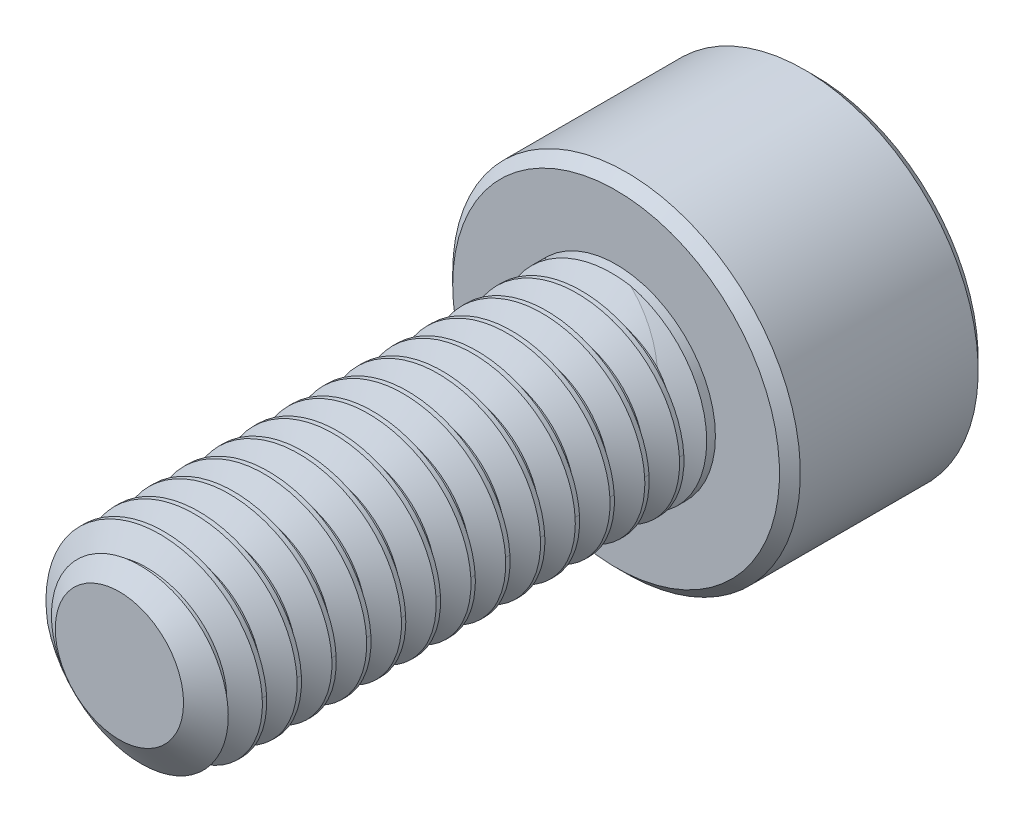
SolidWorks part; units mm, degrees
material "Alloy Steel"
ref_plane "Front Plane" through (0, 0, 0) normal (0, 0, 1) x (1, 0, 0)
ref_plane "Top Plane" through (0, 0, 0) normal (0, 1, 0) x (1, 0, 0)
ref_plane "Right Plane" through (0, 0, 0) normal (1, 0, 0) x (0, 0, -1)
sketch "Sketch1" plane through (0, 0, 0) normal (0, 0, 1) x (1, 0, 0)
  circle A0 centre (0, 0) radius 2
  dimension "OD" = 4
extrude "Extrude1" add sketch "Sketch1" against normal blind 10
sketch "Sketch2" plane through (0, 0, 0) normal (0, 0, 1) x (1, 0, 0)
  circle A0 centre (0, 0) radius 2 construction
  circle A1 centre (0, 0) radius 2
curve "Helix/Spiral1" pitch 0.7 height 10.7 radius 2 centre (0, 0, 0) axis (0, 0, -1) start towards (0, 1, 0) parameters "pitch"=0.7
sketch "Sketch3" plane through (0, 0, 0) normal (1, 0, 0) x (0, 0, -1)
  line L0 (-0.6125, 2) -> (-0.35, 1.5453)
  line L1 (-0.35, 1.5453) -> (-0.2625, 1.5453)
  line L2 (-0.2625, 1.5453) -> (0, 2)
  line L3 (-0.6125, 2) -> (0, 2)
  line L4 (-0.3063, 2) -> (-0.3063, 1.5453) construction
  line L5 (-0.4813, 1.7727) -> (-0.1313, 1.7727) construction
  line L6 (0, 2) -> (0, -2) construction
  line L7 (0, -2) -> (10, -2) construction
  point P11 (3.15, -2)
  dimension "D1" = 0.0875
  dimension "D2" = 0.35
  dimension "D3" = 60
  dimension "D4" = 3.15
sweep "Cut-Sweep1" cut profiles "Sketch3" path "Helix/Spiral1"
sketch "Sketch4" plane through (0, 0, 0) normal (1, 0, 0) x (0, 0, -1)
  line L0 (0.4962, 2) -> (0, 1.2913)
  line L1 (0, 1.2913) -> (0, 2)
  line L2 (0.4962, 2) -> (0, 2)
  line L3 (-0.6125, 2) -> (0, 2) construction
  line L4 (0, 0) -> (7.0209, 0) construction
  dimension "D1" = 55
  dimension "D2" = 0.254
revolve "Cut-Revolve1" cut sketch "Sketch4" angle 360 about L4
sketch "Sketch5" plane through (0, 0, 0) normal (1, 0, 0) x (0, 0, -1)
  line L0 (10, 0.3311) -> (10, 1.814) construction
  line L1 (10, 2) -> (0.1203, 2)
  line L2 (10, 2) -> (10, 0)
  line L3 (10, 0) -> (0.0001, 0)
  line L4 (0.0001, 1.6698) -> (0.0001, 0)
  line L5 (0.1203, 2) -> (0.0001, 1.6698)
  line L6 (0, 0) -> (9.9695, 0) construction
  point P3 (0.0001, 2)
  point P10 (0.0001, 2)
  dimension "D1" = 0.3302
  dimension "Thread min" = 0.0001
  dimension "D3" = 20
revolve "partially thread" [suppressed] add sketch "Sketch5" angle 360 about L6
sketch "Sketch6" plane through (0, 0, -10) normal (0, 0, -1) x (-1, 0, 0)
  circle A0 centre (0, 0) radius 3.5
  dimension "head dia" = 7
extrude "Extrude2" add sketch "Sketch6" along normal blind 4
sketch "Sketch7" plane through (0, 0, -14) normal (0, 0, -1) x (-1, 0, 0)
  line L1 (0, 1.7321) -> (-1.5, 0.866)
  line L2 (-1.5, 0.866) -> (-1.5, -0.866)
  line L3 (-1.5, -0.866) -> (0, -1.7321)
  line L4 (0, -1.7321) -> (1.5, -0.866)
  line L5 (1.5, -0.866) -> (1.5, 0.866)
  line L6 (1.5, 0.866) -> (0, 1.7321)
  circle A0 centre (0, 0) radius 1.5 construction
  dimension "hex dia" = 3
extrude "Cut-Extrude1" cut sketch "Sketch7" against normal blind 2.25
sketch "Sketch8" plane through (0, 0, -14) normal (0, 0, -1) x (-1, 0, 0)
  circle A0 centre (0, 0) radius 1.7321
extrude "Cut-Extrude2" cut sketch "Sketch8" against normal through all draft 45
chamfer "Chamfer1" distance 0.21 angle 45 2 edges at (-3.5, 0, -14) (-3.5, 0, -10)
sketch "Sketch9" plane through (0, 0, 0) normal (1, 0, 0) x (0, 0, -1)
  line L0 (0, 2) -> (0, -2) construction
  line L1 (3.85, 2) -> (3.85, -2) construction
  dimension "D1" = 3.85
sketch "Sketch10" plane through (0, 0, 0) normal (1, 0, 0) x (0, 0, -1)
  line L0 (10, 2) -> (10, 0)
  line L1 (10, 2) -> (9.825, 2)
  line L2 (9.825, 2) -> (8.9966, 0)
  line L3 (10, 0) -> (8.9966, 0)
  line L4 (10, 3.29) -> (10, -3.29) construction
  dimension "D1" = 22.5
  dimension "D2" = 0.175
revolve "Revolve1" add sketch "Sketch10" angle 360 about L3
equation "\"D3@Helix/Spiral1\" = \"screw length@Extrude1\"+\"pitch@Helix/Spiral1\""
equation "\"D1@Sketch3\" = \"pitch@Helix/Spiral1\"*.125"
equation "\"D2@Sketch3\" = \"pitch@Helix/Spiral1\"*.5"
equation "\"D1@Cut-Extrude1\" = \"hex dia@Sketch7\"*.75"
equation "\"D1@Chamfer1\" = \"head dia@Sketch6\"*.03"
equation "\"D1@Sketch9\" = \"pitch@Helix/Spiral1\"*5.5"
equation "\"D2@Sketch10\" = \"pitch@Helix/Spiral1\"*.25"
equation "\"D4@Sketch3\" = \"pitch@Helix/Spiral1\"*4.50"
